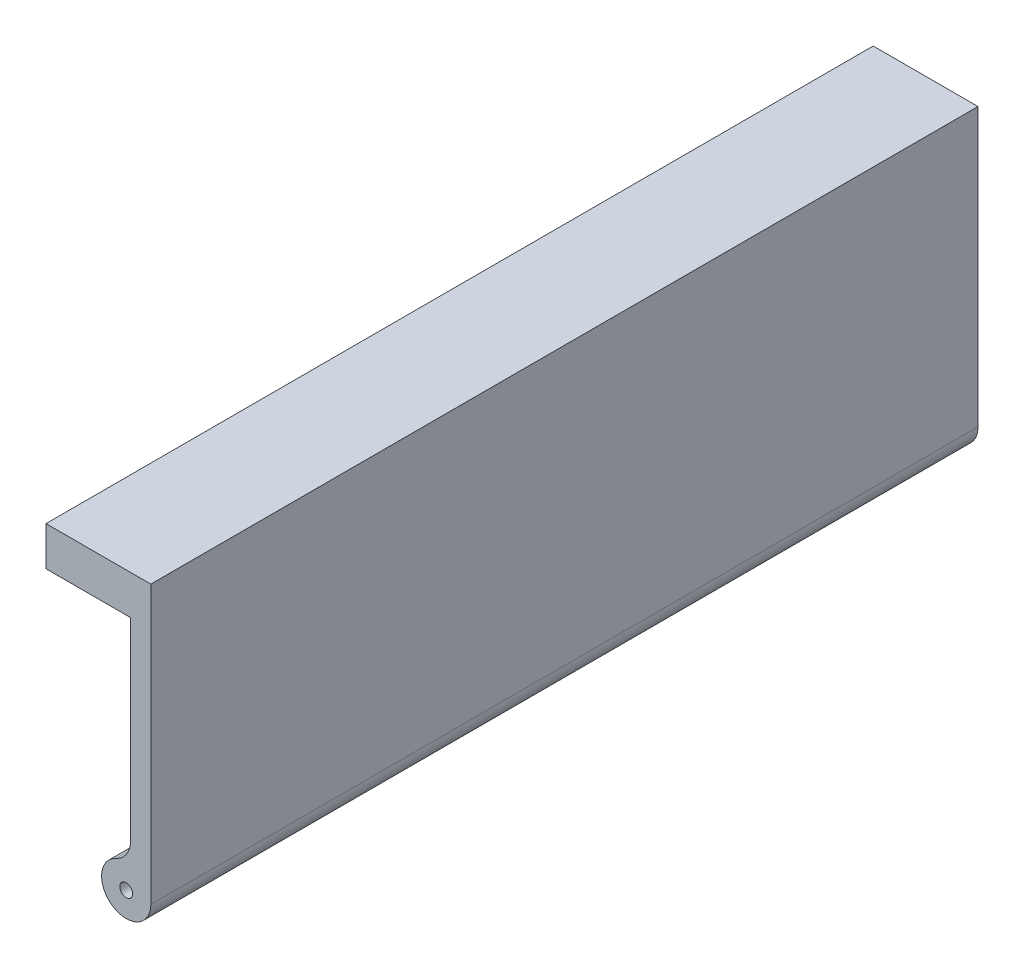
SolidWorks part; units mm, degrees
ref_plane "Front Plane" through (0, 0, 0) normal (0, 0, 1) x (1, 0, 0)
ref_plane "Top Plane" through (0, 0, 0) normal (0, 1, 0) x (1, 0, 0)
ref_plane "Right Plane" through (0, 0, 0) normal (1, 0, 0) x (0, 0, -1)
sketch "Sketch1" plane through (0, 0, 0) normal (0, 0, 1) x (1, 0, 0)
  line L0 (0, 0) -> (3.1723, 0) construction
  line L1 (2.44, 0) -> (2.44, 25)
  line L2 (0.44, 4.49) -> (0.44, 25)
  line L3 (0.44, 25) -> (2.44, 25)
  circle A0 centre (0, 0) radius 0.64
  arc A1 (-1.0175, 2.2177) -> (2.44, 0) centre (0, 0) ccw
  arc A2 (0.44, 4.49) -> (-1.0175, 2.2177) centre (-2.06, 4.49) cw
  dimension "D1" = 1.28
  dimension "D2" = 4.88
  dimension "D5" = 2.5
  dimension "D3" = 25
  dimension "D4" = 2
extrude "Boss-Extrude1" add sketch "Sketch1" along normal blind 82
sketch "Sketch3" plane through (0, 25, 0) normal (0, 1, 0) x (1, 0, 0)
  line L1 (0.44, -82) -> (2.44, -82)
  line L2 (0.44, -82) -> (0.44, 0)
  line L3 (0.44, 0) -> (2.44, 0)
  line L4 (2.44, -82) -> (2.44, 0)
extrude "Boss-Extrude4" add sketch "Sketch3" along normal blind 2.5
sketch "Sketch6" plane through (0.44, 0, 0) normal (-1, 0, 0) x (0, 0, 1)
  line L1 (82, 27.5) -> (0, 27.5)
  line L2 (82, 27.5) -> (82, 23.6193)
  line L3 (82, 23.6193) -> (0, 23.6193)
  line L4 (0, 27.5) -> (0, 23.6193)
  dimension "D1" = 23.01
extrude "Boss-Extrude5" add sketch "Sketch6" along normal blind 8.39
ref_plane "Plane2" through (-7.95, 23.6193, 0) normal (0, 0, 1) x (1, 0, 0)
ref_plane "Plane3" through (-7.95, 23.6193, 82) normal (0, 0, 1) x (1, 0, 0)
sketch "Sketch26" plane through (0, 23.6193, 0) normal (0, -1, 0) x (1, 0, 0)
  line L0 (-7.95, 0) -> (-7.95, 82) construction
  line L1 (-7.95, 33.9228) -> (-5.95, 33.9228)
  line L2 (-7.95, 33.9228) -> (-7.95, 39.9228)
  line L3 (-7.95, 39.9228) -> (-5.95, 39.9228)
  line L4 (-5.95, 33.9228) -> (-5.95, 39.9228)
  line L5 (-6.95, 39.9228) -> (-6.95, 33.9228) construction
  line L6 (-7.95, 36.9228) -> (-5.95, 36.9228) construction
  point P6 (0, 0)
  point P280 (-6.95, 36.9228)
  dimension "D1" = 2
extrude "Cut-Extrude7" cut sketch "Sketch26" against normal blind 2 contours L4 L3 L2 L1
